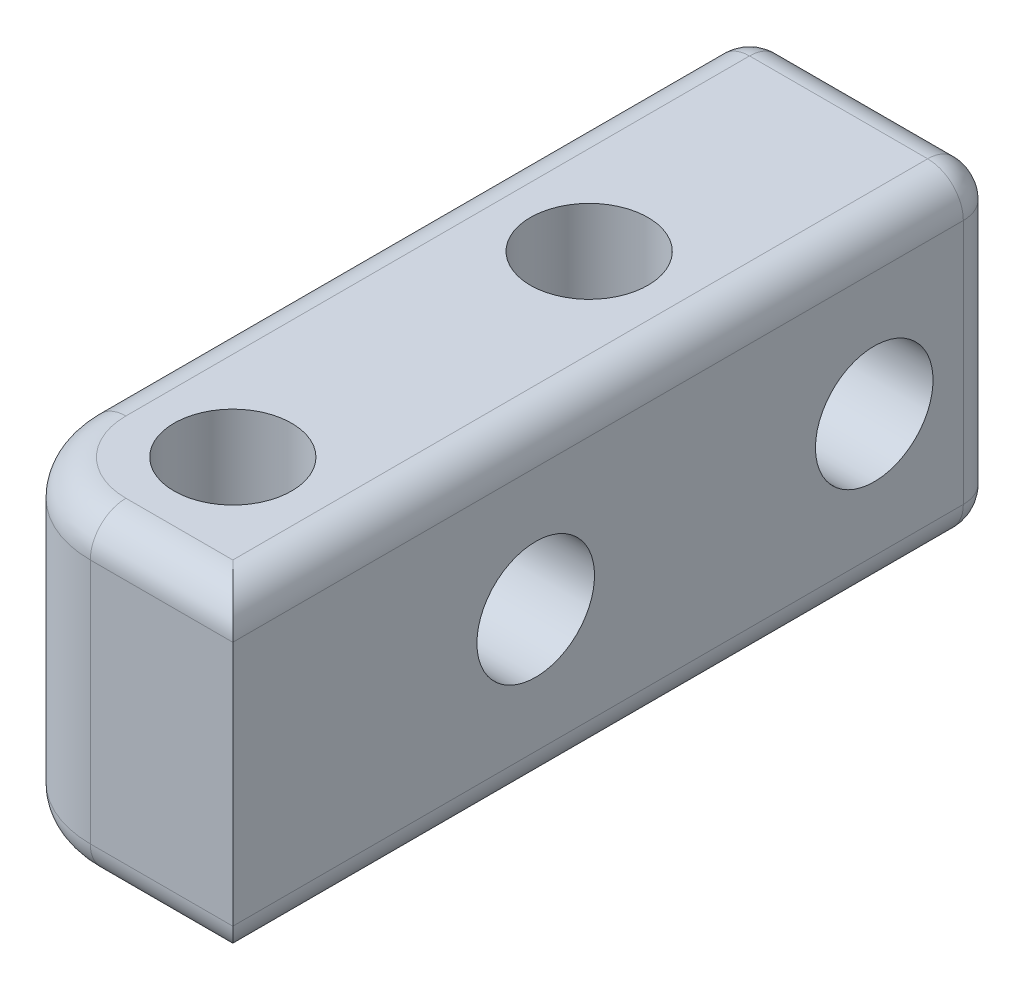
SolidWorks part; units mm, degrees
ref_plane "前视基准面" through (0, 0, 0) normal (0, 0, 1) x (1, 0, 0)
ref_plane "上视基准面" through (0, 0, 0) normal (0, 1, 0) x (1, 0, 0)
ref_plane "右视基准面" through (0, 0, 0) normal (1, 0, 0) x (0, 0, -1)
sketch "草图1" plane through (0, 0, 0) normal (0, 0, 1) x (1, 0, 0)
  line L1 (0, 0) -> (7, 0)
  line L2 (0, 0) -> (0, 8.9)
  line L3 (0, 8.9) -> (7, 8.9)
  line L4 (7, 0) -> (7, 8.9)
  dimension "D1" = 8.9
  dimension "D2" = 7
extrude "凸台-拉伸1" add sketch "草图1" along normal blind 21.5
fillet "圆角1" radius 1 10 edges at (7, 4.45, 0) (0, 4.45, 0) (7, 8.9, 10.75) (3.5, 8.9, 21.5) (0, 8.9, 10.75) (3.5, 8.9, 0) (0, 0, 10.75) (3.5, 0, 21.5) (7, 0, 10.75) (3.5, 0, 0)
sketch "草图6" plane through (0, 0, 0) normal (-1, 0, 0) x (0, 0, 1)
  line L0 (0, 4.45) -> (21.5, 4.45) construction
  line L1 (0, 1) -> (0, 7.9) construction
  line L3 (21.5, 7.9) -> (21.5, 1) construction
  circle A0 centre (3.5, 4.45) radius 1.65
  circle A1 centre (13, 4.45) radius 1.65
  dimension "D1" = 3.3
  dimension "D2" = 3.3
  dimension "D3" = 9.5
  dimension "D4" = 3.5
extrude "切除-拉伸2" cut sketch "草图6" against normal blind 10
sketch "草图7" plane through (0, 8.9, 0) normal (0, 1, 0) x (1, 0, 0)
  circle A0 centre (3.5, -8) radius 1.65
  circle A1 centre (3.5, -18) radius 1.65
  dimension "D1" = 3.3
  dimension "D2" = 3.3
extrude "切除-拉伸3" cut sketch "草图7" against normal blind 10
fillet "圆角3" radius 3 3 edges at (0.2929, 0.2929, 21.2071) (0.2929, 8.6071, 21.2071) (0, 4.45, 21.5)
